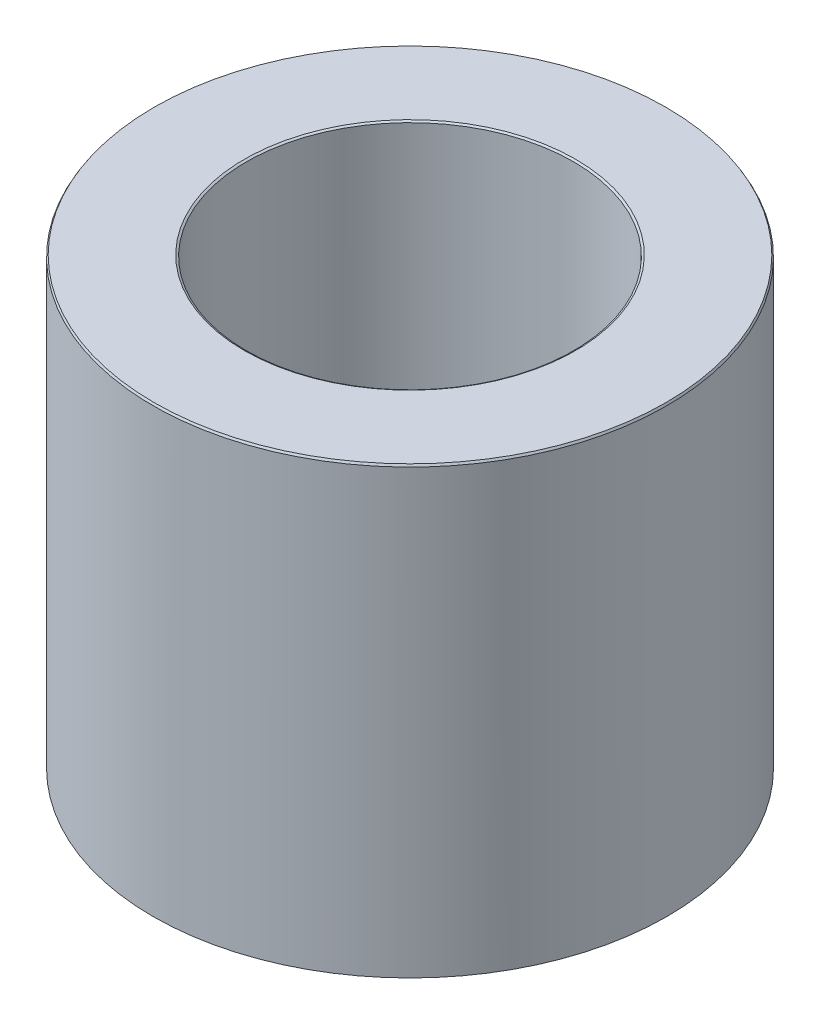
SolidWorks part; units mm, degrees
ref_plane "Front Plane" through (0, 0, 0) normal (0, 0, 1) x (1, 0, 0)
ref_plane "Top Plane" through (0, 0, 0) normal (0, 1, 0) x (1, 0, 0)
ref_plane "Right Plane" through (0, 0, 0) normal (1, 0, 0) x (0, 0, -1)
sketch "Sketch1" plane through (0, 0, 0) normal (0, 1, 0) x (1, 0, 0)
  circle A0 centre (0, 0) radius 45
  dimension "SLEEVE_OD" = 90
extrude "Boss-Extrude1" add sketch "Sketch1" along normal blind 78.022
sketch "Sketch2" plane through (0, 0, 0) normal (0, 1, 0) x (1, 0, 0)
  circle A0 centre (0, 0) radius 28.6532
  dimension "BORE_D" = 57.3064
extrude "Cut-Extrude1" cut sketch "Sketch2" along normal through all
chamfer "Chamfer1" distance 0.3532 angle 30 4 edges at (0, 78.022, 28.6532) (0, 0, 28.6532) (0, 0, 45) (0, 78.022, 45) first distance on face at (0, 78.022, 28.6532) first distance on face at (0, 0, 28.6532) first distance on face at (0, 78.022, 45)
